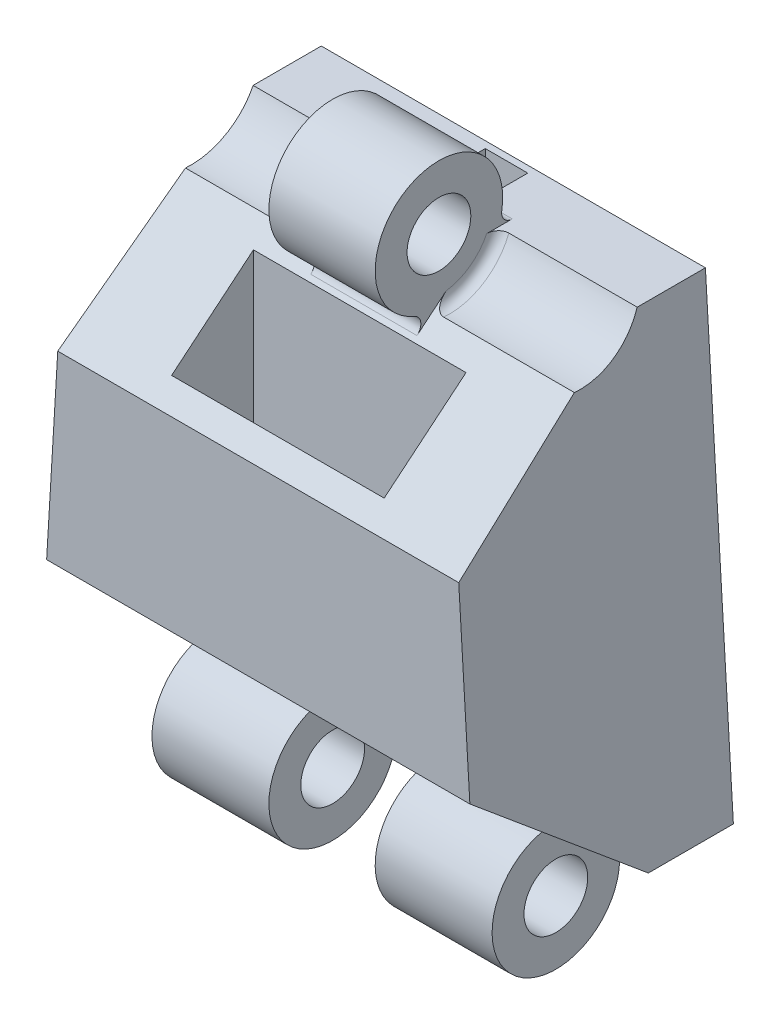
SolidWorks part; units mm, degrees
ref_plane "Front Plane" through (0, 0, 0) normal (0, 0, 1) x (1, 0, 0)
ref_plane "Top Plane" through (0, 0, 0) normal (0, 1, 0) x (1, 0, 0)
ref_plane "Right Plane" through (0, 0, 0) normal (1, 0, 0) x (0, 0, -1)
sketch "Sketch1" plane through (0, 0, 0) normal (0, 0, 1) x (1, 0, 0)
  line L0 (-56.5743, 0) -> (-35.8731, 0)
  line L1 (-55.2587, 22) -> (-37.1887, 22)
  line L2 (-56.5743, 0) -> (-55.2587, 22)
  line L3 (-35.8731, 0) -> (-37.1887, 22)
extrude "Boss-Extrude1" add sketch "Sketch1" along normal blind 12
sketch "Sketch2" plane through (0, 0, 12) normal (0, 0, 1) x (1, 0, 0)
  line L0 (-35.8731, 0) -> (-56.5743, 0)
  line L1 (-46.2237, 0) -> (-46.2237, 29.5391)
ref_plane "Plane1" through (-46.2237, 0, 0) normal (1, 0, 0) x (0, 0, -1)
sketch "Sketch3" plane through (-46.2237, 0, 0) normal (1, 0, 0) x (0, 0, -1)
  line L0 (0, 0) -> (-4, 0)
  line L1 (-12, 0) -> (0, 0) construction
  line L2 (-4, 0) -> (-12, 6.614)
  line L3 (-12, 0) -> (-12, 22) construction
  line L4 (-12, 6.614) -> (-12, 0)
  line L5 (-12, 0) -> (-4, 0)
extrude "Cut-Extrude1" cut sketch "Sketch3" against normal through all both and the other way through all contours L4 L5 L2 region at (-46.2237, 2.2047, 9.3333)
sketch "Sketch6" plane through (-46.2237, 0, 0) normal (1, 0, 0) x (0, 0, -1)
  line L1 (0, 0) -> (-12, 0)
  line L2 (-6, 0) -> (-6, -1.1)
  circle A0 centre (-6, -1.1) radius 1.5
  circle A1 centre (-6, -1.1) radius 3
extrude "Boss-Extrude2" add sketch "Sketch6" along normal mid plane 16 contours L1 A1 A0 | L1 A1 A0 region at (-46.2237, -0.5537, 3.1241) region at (-46.2237, 0.8343, 6)
extrude "Cut-Extrude2" cut sketch "Sketch6<3>" against normal mid plane 5 contours L1 A1 A0 | L1 A1 A0 region at (-46.2237, -0.5537, 3.1241) region at (-46.2237, 0.8343, 6)
sketch "Sketch6<3>" plane through (-46.2237, 0, 0) normal (1, 0, 0) x (0, 0, -1) same geometry as "Sketch6"
sketch "Sketch8" plane through (-46.2237, 0, 0) normal (1, 0, 0) x (0, 0, -1)
  line L0 (0, 22) -> (-4, 22)
  line L1 (-12, 22) -> (0, 22) construction
  line L2 (-4, 22) -> (-12, 15.3704)
  line L3 (-12, 6.614) -> (-12, 22) construction
  line L4 (-12, 15.3704) -> (-12, 22)
  line L5 (-12, 22) -> (-4, 22)
extrude "Cut-Extrude3" cut sketch "Sketch8" against normal through all both and the other way through all contours L5 L4 L2 region at (-46.2237, 19.7901, 9.3333)
sketch "Sketch9" plane through (-46.2237, 0, 0) normal (1, 0, 0) x (0, 0, -1)
  line L0 (-12, 15.3704) -> (-12, 26.5168)
  line L1 (0, 22) -> (-12, 22)
  line L2 (-6, 22) -> (-6, 23.1)
  circle A0 centre (-6, 23.1) radius 1.5
  circle A1 centre (-6, 23.1) radius 3
extrude "Boss-Extrude3" add sketch "Sketch9" along normal mid plane 5 contours L1 A1 A0 | L1 A1 A0 region at (-46.2237, 21.1657, 6) region at (-46.2237, 22.0727, 4.0946)
sketch "Sketch11" plane through (-43.7237, 0, 0) normal (1, 0, 0) x (0, 0, -1)
  circle A0 centre (-6, 23.1) radius 3
extrude "Cut-Extrude4" cut sketch "Sketch11" along normal blind 10
sketch "Sketch12" plane through (-48.7237, 0, 0) normal (-1, 0, 0) x (0, 0, 1)
  circle A0 centre (6, 23.1) radius 3
extrude "Cut-Extrude5" cut sketch "Sketch12" along normal blind 10
fillet "Fillet1" radius 0.5 2 edges at (-46.2237, 22, 3.2089) (-46.2237, 20.1128, 6.2772)
fillet "Fillet2" radius 0.5 2 edges at (-48.7237, 20.5446, 4.4283) (-43.7237, 20.5446, 4.4283)
sketch "Sketch13" plane through (0, 15.008, 12.4372) normal (0, 0.77, 0.6381) x (1, 0, 0)
  line L0 (-46.2237, 0.5678) -> (-46.2237, 1.7678)
  line L2 (-55.6551, 0.5678) -> (-36.7922, 0.5678) construction
  line L3 (-51.2237, 1.7678) -> (-41.2237, 1.7678)
  line L4 (-41.2237, 1.7678) -> (-41.2237, 6.7678)
  line L5 (-41.2237, 6.7678) -> (-51.2237, 6.7678)
  line L6 (-51.2237, 6.7678) -> (-51.2237, 1.7678)
  point P7 (-46.2237, 1.7678)
ref_plane "Plane2" through (0, 10, 0) normal (0, 1, 0) x (1, 0, 0)
sketch "Sketch14" plane through (0, 10, 0) normal (0, 1, 0) x (1, 0, 0)
  line L0 (-51.2237, -7.2262) -> (-51.2237, -11.076)
  line L1 (-51.2237, -11.076) -> (-41.2237, -11.076)
  line L2 (-41.2237, -11.076) -> (-41.2237, -7.2262)
  line L3 (-41.2237, -7.2262) -> (-51.2237, -7.2262)
extrude "Cut-Extrude6" cut sketch "Sketch14" against normal up to surface and the other way up to surface up to face at (-46.2237, 2.0775, 6.5128) other way up to face at (-46.2124, 19.1095, 7.4879)
sketch "Sketch15" plane through (-46.2237, 0, 0) normal (1, 0, 0) x (0, 0, -1)
  line L1 (-4, 0) -> (0, 0) construction
  line L2 (-2.32, 0) -> (-2.32, 24.9106)
  line L3 (-2.32, 24.9106) -> (-0.32, 24.9106)
  line L4 (-0.32, 24.9106) -> (-0.32, -0.7396)
  line L5 (-0.32, -0.7396) -> (-2.32, -0.7396)
  line L6 (-2.32, -0.7396) -> (-2.32, 0)
extrude "Cut-Extrude7" cut sketch "Sketch15" against normal mid plane 2
